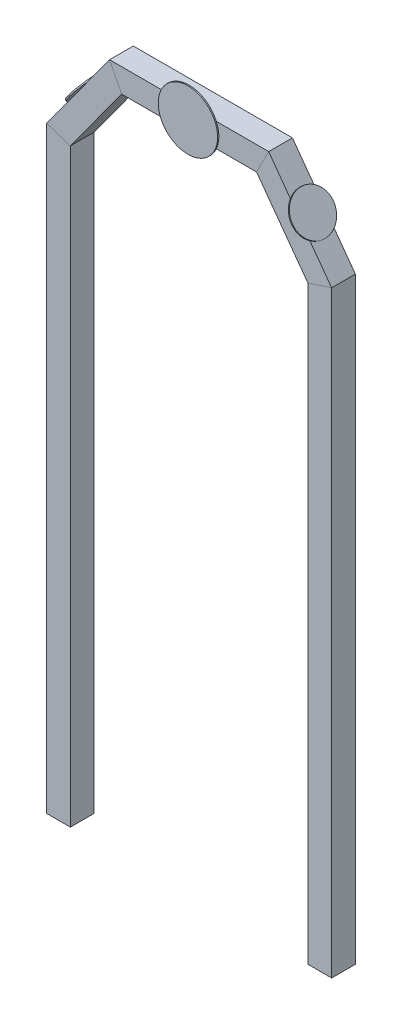
SolidWorks part; units mm, degrees
material "PVC Rigid"
ref_plane "Front Plane" through (0, 0, 0) normal (0, 0, 1) x (1, 0, 0)
ref_plane "Top Plane" through (0, 0, 0) normal (0, 1, 0) x (1, 0, 0)
ref_plane "Right Plane" through (0, 0, 0) normal (1, 0, 0) x (0, 0, -1)
sketch "Sketch1" plane through (0, 0, 0) normal (0, 0, 1) x (1, 0, 0)
  line L0 (330, 0) -> (330, 1500)
  line L1 (330, 1500) -> (185.6711, 1698.2834)
  line L2 (185.6711, 1698.2834) -> (0, 1698.2834)
  dimension "D1" = 330
  dimension "D2" = 1500
sketch "Sketch2" plane through (0, 0, 0) normal (0, 1, 0) x (1, 0, 0)
  line L0 (305, -25) -> (305, 25)
  line L1 (300, -30) -> (360, -30)
  line L2 (300, -30) -> (300, 30)
  line L3 (300, 30) -> (360, 30)
  line L4 (360, -30) -> (360, 30)
  line L5 (300, -30) -> (360, 30) construction
  line L6 (300, 30) -> (360, -30) construction
  line L7 (305, 25) -> (355, 25)
  line L8 (355, -25) -> (355, 25)
  line L9 (305, -25) -> (355, -25)
  point P0 (330, 0)
  dimension "D1" = 60
  dimension "D2" = 60
  dimension "D3" = 5
sweep "Sweep1" add profiles "Sketch2" path "Sketch1"
sketch "Sketch3" plane through (953.666, 694.1658, 0) normal (0.8085, 0.5885, 0) x (0, 0, -1)
  line L0 (0, 1279.0604) -> (0, 1008.7799) construction
  line L1 (30, 1279.0604) -> (-30, 1279.0604) construction
  line L2 (30, 1008.7799) -> (-30, 1008.7799) construction
  circle A0 centre (0, 1143.9201) radius 51.5
  point P8 (0, 1143.9201)
  dimension "D1" = 103
extrude "Boss-Extrude1" add sketch "Sketch3" along normal blind 3
mirror "Mirror1" about plane through (0, 0, 0) normal (1, 0, 0) of "Boss-Extrude1", "Sweep1"
sketch "Sketch4" plane through (0, 0, 30) normal (0, 0, 1) x (1, 0, 0)
  line L0 (-185.6711, 1698.2834) -> (185.6711, 1698.2834) construction
  line L1 (-170.402, 1668.2834) -> (-200.9402, 1728.2834) construction
  line L2 (200.9402, 1728.2834) -> (170.402, 1668.2834) construction
  circle A0 centre (0, 1698.2834) radius 75
  dimension "D1" = 150
extrude "Boss-Extrude2" add sketch "Sketch4" along normal blind 3
